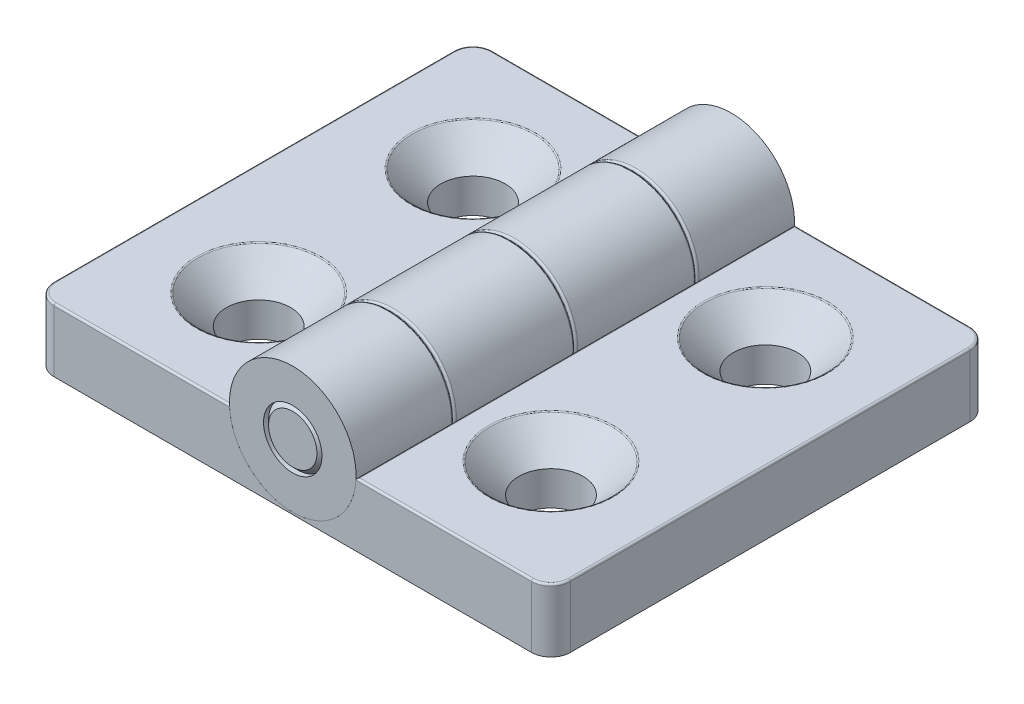
SolidWorks part; units mm, degrees
ref_plane "前视基准面" through (0, 0, 0) normal (0, 0, 1) x (1, 0, 0)
ref_plane "上视基准面" through (0, 0, 0) normal (0, 1, 0) x (1, 0, 0)
ref_plane "右视基准面" through (0, 0, 0) normal (1, 0, 0) x (0, 0, -1)
sketch "草图1" plane through (0, 0, 0) normal (0, 0, 1) x (1, 0, 0)
  circle A0 centre (0, 0) radius 6.5
  circle A1 centre (0, 0) radius 3
  dimension "D1" = 13
  dimension "D2" = 6
extrude "凸台-拉伸1" add sketch "草图1" along normal mid plane 45
sketch "草图2" plane through (0, 0, 0) normal (0, 0, 1) x (1, 0, 0)
  circle A0 centre (0, 0) radius 3
  dimension "D1" = 6
extrude "凸台-拉伸2" add sketch "草图2" along normal mid plane 45 separate body
chamfer "倒角1" distance 0.52 angle 45 1 edges at (3, 0, 22.5)
sketch "草图3" plane through (0, 0, 0) normal (0, 1, 0) x (1, 0, 0)
  line L0 (0, 0) -> (14.2235, 0) construction
  line L1 (7.1978, 12.5) -> (4.6777, 12.5)
  line L2 (7.1978, 12.5) -> (7.1978, 12.4)
  line L3 (7.1978, 12.4) -> (4.6777, 12.4)
  line L4 (4.6777, 12.5) -> (4.6777, 12.4)
  line L5 (6.5, 22.5) -> (-6.5, 22.5) construction
  line L6 (-6.5, -22.5) -> (6.5, -22.5) construction
  line L9 (7.1978, 0.05) -> (4.6777, 0.05)
  line L10 (7.1978, 0.05) -> (7.1978, -0.05)
  line L11 (7.1978, -0.05) -> (4.6777, -0.05)
  line L12 (4.6777, 0.05) -> (4.6777, -0.05)
  line L13 (7.1978, -12.4) -> (4.8947, -12.4)
  line L14 (7.1978, -12.4) -> (7.1978, -12.5)
  line L15 (7.1978, -12.5) -> (4.8947, -12.5)
  line L16 (4.8947, -12.4) -> (4.8947, -12.5)
  point P4 (7.1978, 0)
  dimension "D1" = 10
  dimension "D2" = 0.1
  dimension "D3" = 10
revolve "切除-旋转1" cut sketch "草图3" angle 360 about axis through (0, 0, 22.5) along (0, 0, -1)
fillet "圆角1" radius 0.2 6 edges at (6.5, 0, 12.5) (-6.5, 0, 12.4) (6.5, 0, 0.05) (-6.5, 0, -0.05) (6.5, 0, -12.4) (-6.5, 0, -12.5)
sketch "草图4" plane through (0, 0, 0) normal (0, 1, 0) x (1, 0, 0)
  line L0 (-6.5, -22.5) -> (6.5, -22.5) construction
  line L1 (-19.5, 22.5) -> (19.5, 22.5)
  line L2 (-19.5, 22.5) -> (-19.5, -22.5)
  line L3 (-19.5, -22.5) -> (19.5, -22.5)
  line L4 (19.5, 22.5) -> (19.5, -22.5)
  line L5 (6.5, 22.5) -> (-6.5, 22.5) construction
  point P4 (0, -22.5)
  dimension "D1" = 39
sketch "草图5" plane through (0, 0, -22.5) normal (0, 0, -1) x (-1, 0, 0)
  line L0 (6.4969, -0.2) -> (26.5, -0.2)
  line L3 (-26.5, -0.2) -> (-6.4969, -0.2)
  line L4 (-26.5, -0.2) -> (-26.5, -6.7)
  line L5 (-26.5, -6.7) -> (26.5, -6.7)
  line L6 (26.5, -0.2) -> (26.5, -6.7)
  circle A0 centre (0, 0) radius 6.5 construction
  arc A1 (-6.4969, -0.2) -> (6.4969, -0.2) centre (0, 0) ccw
  dimension "D2" = 0.2
  dimension "D4" = 26.5
  dimension "D1" = 6.5
  dimension "D3" = 53
extrude "凸台-拉伸6" add sketch "草图5" against normal up to surface (45 mm away) separate body up to face at (6.5, 0, 22.5)
hole_wizard "M6 平头机械螺钉的锥形沉头孔1" positions "草图7" profile "草图6" countersink size "M6" standard "Ansi Metric" end condition through all
sketch "草图7" plane through (0, -0.2, 0) normal (0, 1, 0) x (-1, 0, 0)
  line L0 (0, 0) -> (0, 18.3669) construction
  line L2 (0, 0) -> (27.3768, 0) construction
  point P1 (15, -11)
  point P3 (-15, -11)
  point P5 (15, 11)
  point P7 (-15, 11)
  dimension "D1" = 30
  dimension "D2" = 22
sketch "草图6" plane through (-15, -0.2, -11) normal (1, 0, 0) x (0, 0, 1)
  line L0 (0, 0) -> (0, 6.5)
  line L1 (0, 6.5) -> (3.3, 6.5)
  line L2 (3.3, 6.5) -> (3.3, 3)
  line L3 (3.3, 3) -> (6.3, 0)
  line L5 (6.3, 0) -> (0, 0)
  line L6 (-3.3, 3) -> (-6.3, 0) construction
  line L11 (0, -6.35) -> (0, 107.95) construction
  dimension "通孔孔直径" = 6.6
  dimension "通孔孔深度" = 6.5
  dimension "近端锥形沉头孔直径" = 12.6
  dimension "近端锥形沉头孔角度" = 90
fillet "圆角2" radius 0.2 12 edges at (16.4985, -0.2, -22.5) (26.5, -0.2, 0) (16.4985, -0.2, 22.5) (6.4969, -0.2, 0) (15, -0.2, 17.3) (15, -0.2, -4.7) (-16.4985, -0.2, -22.5) (-6.4969, -0.2, 0) (-16.4985, -0.2, 22.5) (-26.5, -0.2, 0) (-15, -0.2, 17.3) (-15, -0.2, -4.7)
fillet "圆角3" radius 2 8 edges at (-26.4414, -0.2586, -22.4414) (26.4414, -0.2586, -22.4414) (26.4414, -0.2586, 22.4414) (-26.4414, -0.2586, 22.4414) (-26.5, -3.55, 22.5) (26.5, -3.55, 22.5) (26.5, -3.55, -22.5) (-26.5, -3.55, -22.5)
chamfer "倒角2" distance 0.5 angle 45 1 edges at (3, 0, -22.5)
